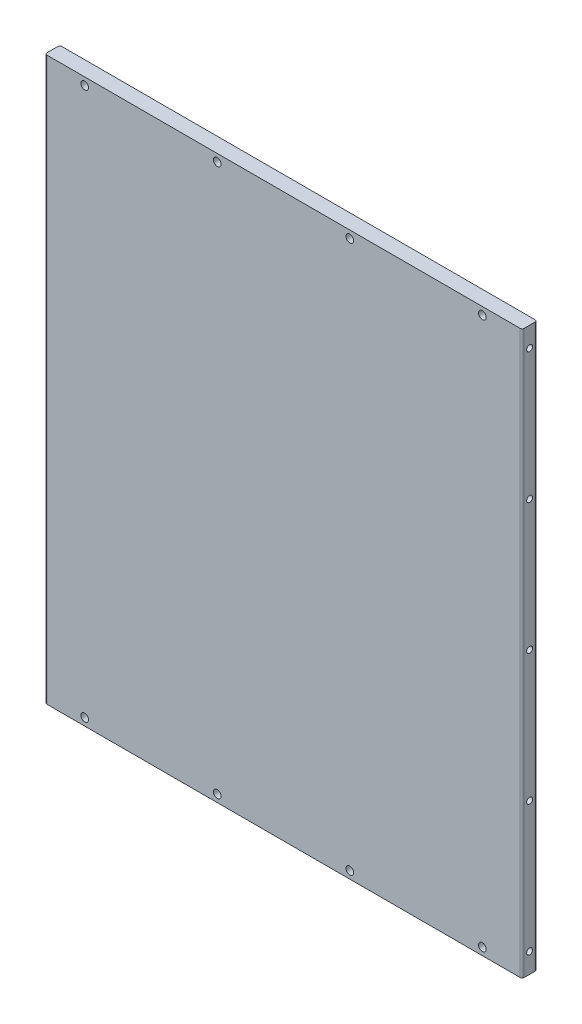
SolidWorks part; units mm, degrees
material "6061 Alloy"
ref_plane "Front Plane" through (0, 0, 0) normal (0, 0, 1) x (1, 0, 0)
ref_plane "Top Plane" through (0, 0, 0) normal (0, 1, 0) x (1, 0, 0)
ref_plane "Right Plane" through (0, 0, 0) normal (1, 0, 0) x (0, 0, -1)
sketch "Sketch1" plane through (0, 0, 0) normal (0, 0, 1) x (1, 0, 0)
  line L0 (6.8, -75) -> (-6.8, -75) construction
  line L1 (49.65, -424.525) -> (-255.15, -424.525)
  line L2 (49.65, -424.525) -> (49.65, -65.475)
  line L3 (49.65, -65.475) -> (-255.15, -65.475)
  line L4 (-255.15, -424.525) -> (-255.15, -65.475)
  line L5 (6.8, -415) -> (-6.8, -415) construction
  line L8 (-102.75, -65.475) -> (-102.75, -135.2471) construction
  line L9 (-78.1066, -135.2471) -> (-127.3934, -135.2471) construction
  dimension "D1" = 9.525
  dimension "D2" = 9.525
  dimension "D3" = 304.8
  dimension "D4" = 359.05
extrude "Boss-Extrude1" add sketch "Sketch1" along normal blind 9.525
hole_wizard "#10-24 Tapped Hole1" positions "Sketch2" profile "Sketch3" tap size "#10-24" standard "ANSI Inch"
sketch "Sketch2" plane through (49.65, 0, 0) normal (1, 0, 0) x (0, 0, -1)
  point P0 (-4.7625, -411.825)
  point P3 (-4.7625, -328.4125)
  point P6 (-4.7625, -245)
  point P9 (-4.7625, -161.5875)
  point P12 (-4.7625, -78.175)
sketch "Sketch3" plane through (49.65, -411.825, 4.7625) normal (0, 1, 0) x (0, 0, -1)
  line L0 (0, 0) -> (0, 20.1908)
  line L1 (0, 20.1908) -> (1.8986, 19.05)
  line L2 (1.8986, 19.05) -> (1.8986, 0)
  line L5 (1.8986, 0) -> (0, 0)
  line L10 (0, 20.1908) -> (-1.8987, 19.05) construction
  line L11 (0, -6.35) -> (0, 107.95) construction
  dimension "Tap Drill Dia." = 3.7973
  dimension "Tap Drill Depth" = 19.05
  dimension "Drill Angle" = 118
cosmetic thread "Hole Thread1" parameters "D1"=15.24, "D2"=4.826
cosmetic thread "Hole Thread2" parameters "D1"=15.24, "D2"=4.826
cosmetic thread "Hole Thread3" parameters "D1"=15.24, "D2"=4.826
cosmetic thread "Hole Thread4" parameters "D1"=15.24, "D2"=4.826
cosmetic thread "Hole Thread5" parameters "D1"=15.24, "D2"=4.826
hole_wizard "#10 (0.1935) Diameter Hole2" positions "Sketch4" profile "Sketch5" hole size "#10" standard "ANSI Inch" end condition through all
sketch "Sketch4" plane through (0, 0, 9.525) normal (0, 0, 1) x (1, 0, 0)
  line L0 (-229.75, -70.2375) -> (-145.0833, -70.2375) construction
  line L1 (-145.0833, -70.2375) -> (-60.4167, -70.2375) construction
  line L2 (-60.4167, -70.2375) -> (24.25, -70.2375) construction
  line L4 (24.25, -419.7625) -> (-60.4167, -419.7625) construction
  line L5 (-60.4167, -419.7625) -> (-145.0833, -419.7625) construction
  line L6 (-145.0833, -419.7625) -> (-229.75, -419.7625) construction
  line L8 (49.65, -65.475) -> (-255.15, -65.475) construction
  line L9 (49.65, -65.475) -> (-255.15, -65.475) construction
  line L10 (-255.15, -424.525) -> (49.65, -424.525) construction
  line L11 (-255.15, -424.525) -> (49.65, -424.525) construction
  point P0 (-229.75, -70.2375)
  point P2 (-145.0833, -70.2375)
  point P4 (-60.4167, -70.2375)
  point P6 (24.25, -70.2375)
  point P8 (-229.75, -419.7625)
  point P10 (-145.0833, -419.7625)
  point P12 (-60.4167, -419.7625)
  point P14 (24.25, -419.7625)
  point P26 (-102.75, -419.7625)
  point P27 (-102.75, -70.2375)
  dimension "D1" = 25.4
  dimension "D2" = 25.4
  dimension "D3" = 4.7625
  dimension "D4" = 4.7625
sketch "Sketch5" plane through (-229.75, -70.2375, 9.525) normal (1, 0, 0) x (0, -1, 0)
  line L0 (0, 0) -> (0, 9.525)
  line L1 (0, 9.525) -> (2.4574, 9.525)
  line L2 (2.4574, 9.525) -> (2.4574, 0)
  line L5 (2.4574, 0) -> (0, 0)
  line L11 (0, -6.35) -> (0, 107.95) construction
  dimension "Thru Hole Dia." = 4.9149
  dimension "Thru Hole Depth" = 9.525
ref_plane "Plane1" through (-102.75, 0, 0) normal (1, 0, 0) x (0, 0, -1)
mirror "Mirror1" about plane through (-102.75, 0, 0) normal (1, 0, 0) of "#10-24 Tapped Hole1"
cosmetic thread "Hole Thread14" parameters "D1"=15.24, "D2"=4.826
cosmetic thread "Hole Thread15" parameters "D1"=15.24, "D2"=4.826
cosmetic thread "Hole Thread16" parameters "D1"=15.24, "D2"=4.826
cosmetic thread "Hole Thread17" parameters "D1"=15.24, "D2"=4.826
cosmetic thread "Hole Thread18" parameters "D1"=15.24, "D2"=4.826
fillet "Fillet1" [suppressed] radius 1.27
fillet "Fillet2" radius 1.27 4 edges at (-255.15, -245, 0) (-255.15, -245, 9.525) (49.65, -245, 0) (49.65, -245, 9.525)
equation "\"D2@Sketch1\"=\"D1@Sketch1\""
equation "\"D2@Sketch4\"=\"D1@Sketch4\""
equation "\"D4@Sketch4\"=\"D3@Sketch4\""
